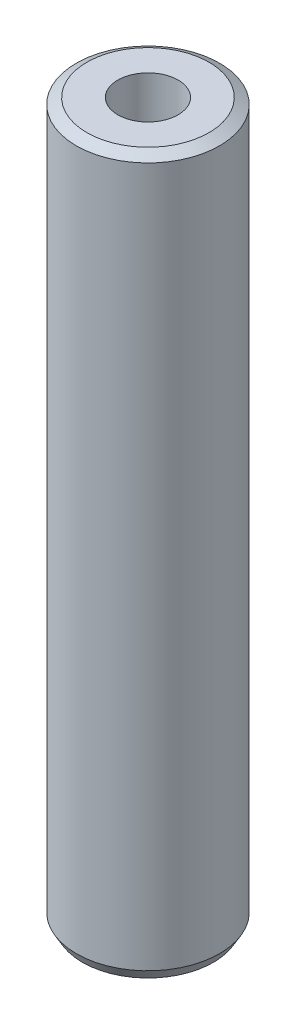
SolidWorks part; units mm, degrees
ref_plane "Front Plane" through (0, 0, 0) normal (0, 0, 1) x (1, 0, 0)
ref_plane "Top Plane" through (0, 0, 0) normal (0, 1, 0) x (1, 0, 0)
ref_plane "Right Plane" through (0, 0, 0) normal (1, 0, 0) x (0, 0, -1)
sketch "Sketch1" plane through (0, 0, 0) normal (0, 1, 0) x (1, 0, 0)
  circle A0 centre (0, 0) radius 60
  dimension "SHAFT_OD" = 120
extrude "Boss-Extrude1" add sketch "Sketch1" along normal blind 600
sketch "Sketch2" plane through (0, 0, 0) normal (0, 1, 0) x (1, 0, 0)
  circle A0 centre (0, 0) radius 25.2598
  dimension "BORE_D" = 50.5197
extrude "Cut-Extrude1" cut sketch "Sketch2" along normal through all
chamfer "Chamfer1" distance 5.1176 angle 60 2 edges at (0, 600, 60) (0, 0, 60) first distance on face at (0, 600, 60) first distance on face at (0, 0, 25.2598)
